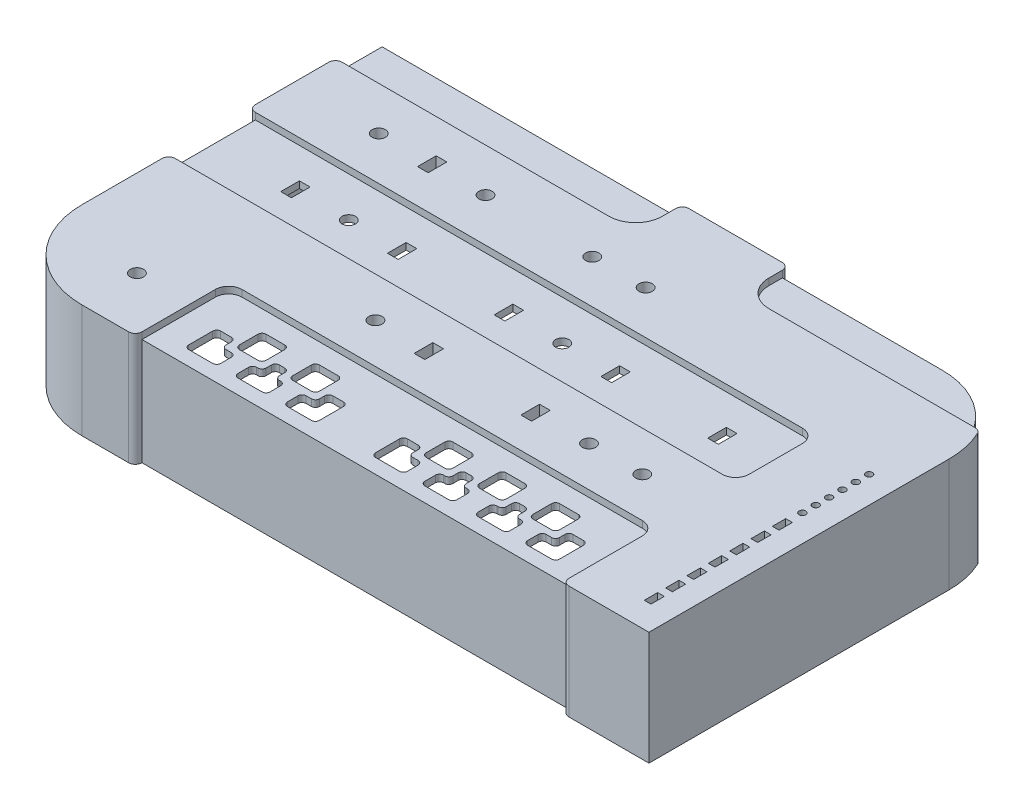
SolidWorks part; units mm, degrees
ref_plane "Front Plane" through (0, 0, 0) normal (0, 0, 1) x (1, 0, 0)
ref_plane "Top Plane" through (0, 0, 0) normal (0, 1, 0) x (1, 0, 0)
ref_plane "Right Plane" through (0, 0, 0) normal (1, 0, 0) x (0, 0, -1)
sketch "Sketch1" plane through (0, 0, 0) normal (0, 1, 0) x (1, 0, 0)
  line L1 (0, 0) -> (240, 0)
  line L2 (0, 0) -> (0, 140)
  line L3 (0, 140) -> (240, 140)
  line L4 (240, 0) -> (240, 140)
  dimension "D1" = 240
  dimension "D2" = 140
extrude "Boss-Extrude1" add sketch "Sketch1" along normal blind 40
fillet "Fillet1" radius 30 2 edges at (240, 20, -140) (0, 20, 0)
sketch "Sketch2" plane through (0, 0, 0) normal (0, -1, 0) x (1, 0, 0)
  line L4 (110, -142.5) -> (110, -125)
  line L5 (110, -125) -> (-2.5, -125)
  line L6 (150, -142.5) -> (150, -125)
  line L7 (150, -125) -> (238.8314, -125)
  line L8 (242.5, -110) -> (242.5, 2.5)
  line L9 (-2.5, -142.5) -> (210, -142.5)
  line L10 (-2.5, -30) -> (-2.5, -142.5)
  line L11 (242.5, 2.5) -> (30, 2.5)
  line L12 (242.5, -110) -> (242.5, 2.5)
  line L13 (110, -142.5) -> (150, -142.5)
  line L14 (-2.5, -30) -> (-2.5, -62.5)
  line L15 (242.5, 2.5) -> (210, 2.5)
  line L16 (-2.5, -92.5) -> (210, -92.5)
  line L17 (210, -92.5) -> (210, -62.5)
  line L18 (210, -62.5) -> (-2.5, -62.5)
  line L19 (50, 2.5) -> (50, -32.5)
  line L20 (50, -32.5) -> (210, -32.5)
  line L21 (210, -32.5) -> (210, 2.5)
  line L22 (210, -140) -> (0, -140) construction
  line L23 (50, 2.5) -> (30, 2.5)
  line L24 (-2.5, -92.5) -> (-2.5, -125)
  arc A4 (210, -142.5) -> (242.5, -110) centre (210, -110) ccw
  arc A5 (30, 2.5) -> (-2.5, -30) centre (30, -30) ccw
  arc A6 (238.8314, -125) -> (242.5, -110) centre (210, -110) ccw
  arc A7 (30, 2.5) -> (-2.5, -30) centre (30, -30) ccw
  point P24 (150, -133.75)
  dimension "D2" = 35
  dimension "D3" = 30
  dimension "D4" = 30
  dimension "D5" = 15
  dimension "D6" = 60
  dimension "D7" = 40
  dimension "D8" = 60
  dimension "D1" = 2.5
extrude "Boss-Extrude2" add sketch "Sketch2" against normal offset from surface (42.5 mm away) 2.5 up to face at (120, 40, -70) offset beyond the face yes
sketch "Sketch3" plane through (0, 0, 0) normal (0, -1, 0) x (1, 0, 0)
  line L38 (2.5, -57.5) -> (5, -57.5)
  line L39 (5, -57.5) -> (5, -97.5)
  line L40 (5, -97.5) -> (2.5, -97.5)
  line L41 (2.5, -97.5) -> (2.5, -120)
  line L42 (2.5, -120) -> (5, -120)
  line L43 (5, -120) -> (5, -135)
  line L44 (5, -135) -> (115, -135)
  line L45 (115, -135) -> (115, -137.5)
  line L46 (115, -137.5) -> (145, -137.5)
  line L47 (145, -137.5) -> (145, -135)
  line L48 (145, -135) -> (210, -135)
  line L49 (232.9129, -120) -> (235.6174, -120)
  line L50 (237.5, -110) -> (237.5, -2.5)
  line L51 (237.5, -2.5) -> (215, -2.5)
  line L52 (215, -2.5) -> (215, -5)
  line L53 (215, -5) -> (45, -5)
  line L54 (45, -5) -> (45, -2.5)
  line L55 (45, -2.5) -> (30, -2.5)
  line L56 (2.5, -30) -> (2.5, -57.5)
  line L57 (2.5, -57.5) -> (5, -57.5)
  line L58 (5, -57.5) -> (5, -97.5)
  line L59 (5, -97.5) -> (2.5, -97.5)
  line L60 (2.5, -97.5) -> (2.5, -120)
  line L61 (2.5, -120) -> (5, -120)
  line L62 (5, -120) -> (5, -135)
  line L63 (5, -135) -> (115, -135)
  line L64 (115, -135) -> (115, -137.5)
  line L65 (115, -137.5) -> (145, -137.5)
  line L66 (145, -137.5) -> (145, -135)
  line L67 (145, -135) -> (210, -135)
  line L68 (232.9129, -120) -> (235.6174, -120)
  line L69 (237.5, -110) -> (237.5, -2.5)
  line L70 (237.5, -2.5) -> (215, -2.5)
  line L71 (215, -2.5) -> (215, -5)
  line L72 (215, -5) -> (45, -5)
  line L73 (45, -5) -> (45, -2.5)
  line L74 (45, -2.5) -> (30, -2.5)
  line L75 (2.5, -30) -> (2.5, -57.5)
  arc A6 (210, -135) -> (232.9129, -120) centre (210, -110) ccw
  arc A7 (235.6174, -120) -> (237.5, -110) centre (210, -110) ccw
  arc A8 (30, -2.5) -> (2.5, -30) centre (30, -30) ccw
  arc A9 (210, -135) -> (232.9129, -120) centre (210, -110) ccw
  arc A10 (235.6174, -120) -> (237.5, -110) centre (210, -110) ccw
  arc A11 (30, -2.5) -> (2.5, -30) centre (30, -30) ccw
  dimension "D1" = 5
extrude "Cut-Extrude1" cut sketch "Sketch3" against normal offset from surface (37.5 mm away) 5 up to face at (122.1113, 42.5, -71.305)
fillet "Fillet2" radius 10 1 edges at (110, 41.25, -125)
fillet "Fillet3" radius 10 1 edges at (150, 41.25, -125)
fillet "Fillet4" radius 5 2 edges at (210, 41.25, -62.5) (210, 41.25, -92.5)
fillet "Fillet5" radius 5 2 edges at (210, 41.25, -32.5) (50, 41.25, -32.5)
fillet "Fillet6" radius 2.5 8 edges at (-2.5, 21.25, -125) (-2.5, 21.25, -92.5) (-2.5, 21.25, -62.5) (50, 21.25, 2.5) (210, 21.25, 2.5) (238.8314, 21.25, -125) (150, 21.25, -142.5) (110, 21.25, -142.5)
sketch "Sketch4" plane through (0, 42.5, 0) normal (0, 1, 0) x (1, 0, 0)
  line L0 (120, 140) -> (120, 0) construction
  line L1 (110, 140) -> (0, 140) construction
  line L2 (50, 0) -> (210, 0) construction
  line L3 (0, 92.5) -> (0, 62.5) construction
  line L4 (50, 0) -> (50, 27.5) construction
  line L5 (48, 112.25) -> (52, 112.25)
  line L6 (48, 112.25) -> (48, 105.25)
  line L7 (48, 105.25) -> (52, 105.25)
  line L8 (52, 112.25) -> (52, 105.25)
  line L9 (28, 81) -> (32, 81)
  line L10 (28, 81) -> (28, 74)
  line L11 (28, 74) -> (32, 74)
  line L12 (32, 81) -> (32, 74)
  line L13 (68, 81) -> (72, 81)
  line L14 (68, 81) -> (68, 74)
  line L15 (68, 74) -> (72, 74)
  line L16 (72, 81) -> (72, 74)
  line L17 (108, 81) -> (112, 81)
  line L18 (108, 81) -> (108, 74)
  line L19 (108, 74) -> (112, 74)
  line L20 (112, 81) -> (112, 74)
  line L21 (148, 81) -> (152, 81)
  line L22 (148, 81) -> (148, 74)
  line L23 (148, 74) -> (152, 74)
  line L24 (152, 81) -> (152, 74)
  line L25 (188, 81) -> (192, 81)
  line L26 (188, 81) -> (188, 74)
  line L27 (188, 74) -> (192, 74)
  line L28 (192, 81) -> (192, 74)
  line L29 (108, 51) -> (112, 51)
  line L30 (108, 51) -> (108, 44)
  line L31 (108, 44) -> (112, 44)
  line L32 (112, 51) -> (112, 44)
  line L33 (148, 51) -> (152, 51)
  line L34 (148, 51) -> (148, 44)
  line L35 (148, 44) -> (152, 44)
  line L36 (152, 51) -> (152, 44)
  line L37 (110, 135) -> (110, 140) construction
  line L38 (110, 140) -> (110, 135) construction
  line L40 (147.5, 142.5) -> (112.5, 142.5) construction
  line L41 (150, 140) -> (150, 135) construction
  line L42 (210, 0) -> (210, 27.5) construction
  line L44 (-2.5, 47.5) -> (242.5, 47.5) construction
  line L45 (-2.5, 60) -> (-2.5, 30) construction
  line L46 (242.5, -2.5) -> (242.5, 110) construction
  line L47 (205, 62.5) -> (0, 62.5) construction
  line L48 (205, 32.5) -> (55, 32.5) construction
  line L49 (0, 77.5) -> (210, 77.5) construction
  line L50 (210, 67.5) -> (210, 87.5) construction
  line L51 (-2.5, 108.75) -> (242.5, 108.75) construction
  line L52 (-2.5, 122.5) -> (-2.5, 95) construction
  circle A0 centre (30, 108.75) radius 2.5
  circle A1 centre (70, 108.75) radius 2.5
  circle A2 centre (110, 108.75) radius 2.5
  circle A3 centre (130, 108.75) radius 2.5
  circle A4 centre (130, 77.5) radius 2.5
  circle A5 centre (190, 47.5) radius 2.5
  circle A6 centre (170, 47.5) radius 2.5
  circle A7 centre (90, 47.5) radius 2.5
  circle A8 centre (30, 18.1) radius 2.5
  circle A9 centre (50, 77.5) radius 2.5
  point P55 (30, 81)
  point P57 (50, 105.25)
  point P58 (150, 74)
  point P59 (70, 81)
  point P60 (150, 51)
  point P61 (110, 81)
  point P62 (110, 51)
  point P63 (110, 74)
  point P64 (190, 74)
  point P71 (70, 74)
  point P74 (110, 137.5)
  point P81 (130, 142.5)
  point P85 (150, 81)
  point P105 (48, 108.75)
  point P107 (28, 77.5)
  point P108 (68, 77.5)
  point P109 (108, 77.5)
  point P110 (148, 77.5)
  point P111 (188, 77.5)
  point P116 (108, 47.5)
  point P117 (148, 47.5)
  dimension "D2" = 5
  dimension "D10" = 20
  dimension "D1" = 120
  dimension "D3" = 4
  dimension "D4" = 7
  dimension "D5" = 20
  dimension "D6" = 20
  dimension "D7" = 20
  dimension "D8" = 20
  dimension "D9" = 18.1
extrude "Cut-Extrude2" cut sketch "Sketch4" against normal through all
sketch "Sketch5" plane through (0, 40, 0) normal (0, 1, 0) x (1, 0, 0)
  line L0 (120, 140) -> (120, 0) construction
  line L1 (110, 140) -> (0, 140) construction
  line L2 (50, 0) -> (210, 0) construction
  line L3 (-2.5, 122.5) -> (-2.5, 95) construction
  line L4 (242.5, -2.5) -> (242.5, 110) construction
  line L5 (85, 32.5) -> (85, 0) construction
  line L6 (70, 25) -> (80, 25)
  line L7 (70, 25) -> (70, 15)
  line L8 (70, 15) -> (80, 15)
  line L9 (80, 25) -> (80, 15)
  line L10 (90, 25) -> (100, 25)
  line L11 (90, 25) -> (90, 15)
  line L12 (90, 15) -> (100, 15)
  line L13 (100, 25) -> (100, 15)
  line L14 (140, 25) -> (150, 25)
  line L15 (140, 25) -> (140, 15)
  line L16 (140, 15) -> (150, 15)
  line L17 (150, 25) -> (150, 15)
  line L18 (160, 25) -> (170, 25)
  line L19 (160, 25) -> (160, 15)
  line L20 (160, 15) -> (170, 15)
  line L21 (170, 25) -> (170, 15)
  line L22 (180, 25) -> (190, 25)
  line L23 (180, 25) -> (180, 15)
  line L24 (180, 15) -> (190, 15)
  line L25 (190, 25) -> (190, 15)
  line L26 (55, 32.5) -> (205, 32.5) construction
  line L27 (205, 32.5) -> (55, 32.5) construction
  line L28 (50, 27.5) -> (50, 0) construction
  line L29 (165, 32.5) -> (165, 0) construction
  point P40 (165, 25)
  dimension "D1" = 10
  dimension "D2" = 10
  dimension "D3" = 35
  dimension "D4" = 5
  dimension "D5" = 7.5
  dimension "D6" = 45
  dimension "D7" = 10
  dimension "D8" = 10
extrude "Cut-Extrude3" cut sketch "Sketch5" against normal through all
sketch "Sketch6" plane through (0, 40, 0) normal (0, 1, 0) x (1, 0, 0)
  line L0 (60.5, 17.5) -> (67.5, 17.5)
  line L1 (67.5, 17.5) -> (67.5, 12.5)
  line L2 (67.5, 12.5) -> (72.5, 12.5)
  line L3 (72.5, 12.5) -> (72.5, 5.5)
  line L4 (72.5, 5.5) -> (60.5, 5.5)
  line L5 (60.5, 5.5) -> (60.5, 17.5)
  line L6 (82.5, 17.5) -> (82.5, 12.5)
  line L7 (82.5, 12.5) -> (79, 12.5)
  line L8 (79, 12.5) -> (79, 5.5)
  line L9 (79, 5.5) -> (91, 5.5)
  line L10 (91, 5.5) -> (91, 12.5)
  line L11 (91, 12.5) -> (87.5, 12.5)
  line L12 (87.5, 12.5) -> (87.5, 17.5)
  line L13 (87.5, 17.5) -> (82.5, 17.5)
  line L14 (97.5, 12.5) -> (102.5, 12.5)
  line L15 (102.5, 12.5) -> (102.5, 17.5)
  line L16 (102.5, 17.5) -> (109.5, 17.5)
  line L17 (109.5, 17.5) -> (109.5, 5.5)
  line L18 (109.5, 5.5) -> (97.5, 5.5)
  line L19 (97.5, 5.5) -> (97.5, 12.5)
  line L20 (137.5, 17.5) -> (137.5, 12.5)
  line L21 (137.5, 12.5) -> (142.5, 12.5)
  line L22 (142.5, 12.5) -> (142.5, 5.5)
  line L23 (142.5, 5.5) -> (130.5, 5.5)
  line L24 (130.5, 5.5) -> (130.5, 17.5)
  line L25 (130.5, 17.5) -> (137.5, 17.5)
  line L26 (152.5, 17.5) -> (152.5, 12.5)
  line L27 (152.5, 12.5) -> (149, 12.5)
  line L28 (149, 12.5) -> (149, 5.5)
  line L29 (149, 5.5) -> (161, 5.5)
  line L30 (161, 5.5) -> (161, 12.5)
  line L31 (161, 12.5) -> (157.5, 12.5)
  line L32 (157.5, 12.5) -> (157.5, 17.5)
  line L33 (157.5, 17.5) -> (152.5, 17.5)
  line L34 (172.5, 17.5) -> (172.5, 12.5)
  line L35 (172.5, 12.5) -> (169, 12.5)
  line L36 (169, 12.5) -> (169, 5.5)
  line L37 (169, 5.5) -> (181, 5.5)
  line L38 (181, 5.5) -> (181, 12.5)
  line L39 (181, 12.5) -> (177.5, 12.5)
  line L40 (177.5, 12.5) -> (177.5, 17.5)
  line L41 (177.5, 17.5) -> (172.5, 17.5)
  line L42 (187.5, 12.5) -> (192.5, 12.5)
  line L43 (192.5, 12.5) -> (192.5, 17.5)
  line L44 (192.5, 17.5) -> (199.5, 17.5)
  line L45 (199.5, 17.5) -> (199.5, 5.5)
  line L46 (199.5, 5.5) -> (187.5, 5.5)
  line L47 (187.5, 5.5) -> (187.5, 12.5)
  line L48 (70, 25) -> (70, 15) construction
  line L49 (70, 15) -> (80, 15) construction
  line L50 (80, 15) -> (80, 25) construction
  line L51 (90, 25) -> (90, 15) construction
  line L52 (100, 15) -> (100, 25) construction
  line L54 (140, 25) -> (140, 15) construction
  line L55 (190, 15) -> (190, 25) construction
  line L56 (150, 15) -> (150, 25) construction
  line L57 (170, 15) -> (170, 25) construction
  point P53 (82.5, 15)
  dimension "D1" = 12
  dimension "D2" = 2.5
  dimension "D3" = 2.5
  dimension "D4" = 12
  dimension "D5" = 2.5
  dimension "D6" = 2.5
  dimension "D7" = 2.5
  dimension "D8" = 2.5
  dimension "D9" = 2.5
  dimension "D10" = 1
  dimension "D11" = 2.5
  dimension "D12" = 2.5
  dimension "D13" = 2.5
  dimension "D14" = 2.5
  dimension "D15" = 2.5
  dimension "D16" = 1
  dimension "D17" = 1
extrude "Cut-Extrude4" cut sketch "Sketch6" against normal through all
fillet "Fillet8" radius 1.5 8 edges at (79, 38.75, -12.5) (82.5, 38.75, -12.5) (82.5, 38.75, -17.5) (102.5, 38.75, -12.5) (102.5, 38.75, -17.5) (90, 38.75, -25) (70, 38.75, -25) (60.5, 38.75, -17.5)
fillet "Fillet9" radius 1.5 9 edges at (109.5, 38.75, -17.5) (100, 38.75, -25) (91, 38.75, -12.5) (87.5, 38.75, -12.5) (87.5, 38.75, -17.5) (80, 38.75, -25) (72.5, 38.75, -12.5) (67.5, 38.75, -12.5) (67.5, 38.75, -17.5)
fillet "Fillet10" radius 1.5 1 edges at (97.5, 38.75, -12.5)
fillet "Fillet11" radius 1.5 13 edges at (192.5, 38.75, -17.5) (192.5, 38.75, -12.5) (187.5, 38.75, -12.5) (169, 38.75, -12.5) (172.5, 38.75, -12.5) (172.5, 38.75, -17.5) (180, 38.75, -25) (160, 38.75, -25) (152.5, 38.75, -17.5) (152.5, 38.75, -12.5) (149, 38.75, -12.5) (140, 38.75, -25) (130.5, 38.75, -17.5)
fillet "Fillet12" radius 1.5 13 edges at (199.5, 38.75, -17.5) (190, 38.75, -25) (181, 38.75, -12.5) (177.5, 38.75, -12.5) (177.5, 38.75, -17.5) (170, 38.75, -25) (161, 38.75, -12.5) (157.5, 38.75, -12.5) (157.5, 38.75, -17.5) (150, 38.75, -25) (142.5, 38.75, -12.5) (137.5, 38.75, -12.5) (137.5, 38.75, -17.5)
fillet "Fillet13" radius 1.5 12 edges at (109.5, 38.75, -5.5) (100, 38.75, -15) (91, 38.75, -5.5) (80, 38.75, -15) (72.5, 38.75, -5.5) (142.5, 38.75, -5.5) (150, 38.75, -15) (161, 38.75, -5.5) (170, 38.75, -15) (181, 38.75, -5.5) (190, 38.75, -15) (199.5, 38.75, -5.5)
fillet "Fillet14" radius 1.5 12 edges at (90, 38.75, -15) (70, 38.75, -15) (60.5, 38.75, -5.5) (79, 38.75, -5.5) (97.5, 38.75, -5.5) (130.5, 38.75, -5.5) (140, 38.75, -15) (149, 38.75, -5.5) (160, 38.75, -15) (169, 38.75, -5.5) (180, 38.75, -15) (187.5, 38.75, -5.5)
sketch "Sketch7" plane through (0, 42.5, 0) normal (0, 1, 0) x (1, 0, 0)
  line L0 (210, 77.5) -> (245.2307, 77.5) construction
  line L1 (231.25, 60) -> (233.75, 60)
  line L2 (231.25, 60) -> (231.25, 55)
  line L3 (231.25, 55) -> (233.75, 55)
  line L4 (233.75, 60) -> (233.75, 55)
  line L5 (231.25, 52) -> (233.75, 52)
  line L6 (231.25, 52) -> (231.25, 47)
  line L7 (231.25, 47) -> (233.75, 47)
  line L8 (233.75, 52) -> (233.75, 47)
  line L9 (231.25, 44) -> (233.75, 44)
  line L10 (231.25, 44) -> (231.25, 39)
  line L11 (231.25, 39) -> (233.75, 39)
  line L12 (233.75, 44) -> (233.75, 39)
  line L13 (231.25, 36) -> (233.75, 36)
  line L14 (231.25, 36) -> (231.25, 31)
  line L15 (231.25, 31) -> (233.75, 31)
  line L16 (233.75, 36) -> (233.75, 31)
  line L17 (231.25, 28) -> (233.75, 28)
  line L18 (231.25, 28) -> (231.25, 23)
  line L19 (231.25, 23) -> (233.75, 23)
  line L20 (233.75, 28) -> (233.75, 23)
  line L21 (231.25, 20) -> (233.75, 20)
  line L22 (231.25, 20) -> (231.25, 15)
  line L23 (231.25, 15) -> (233.75, 15)
  line L24 (233.75, 20) -> (233.75, 15)
  line L25 (231.25, 12) -> (233.75, 12)
  line L26 (231.25, 12) -> (231.25, 7)
  line L27 (231.25, 7) -> (233.75, 7)
  line L28 (233.75, 12) -> (233.75, 7)
  line L29 (210, 87.5) -> (210, 67.5) construction
  line L30 (242.5, -2.5) -> (242.5, 110) construction
  circle A0 centre (232.5, 90) radius 1.25
  circle A1 centre (232.5, 85) radius 1.25
  circle A2 centre (232.5, 80) radius 1.25
  circle A3 centre (232.5, 75) radius 1.25
  circle A4 centre (232.5, 70) radius 1.25
  circle A5 centre (232.5, 65) radius 1.25
  point P42 (232.5, 60)
  point P43 (232.5, 52)
  point P44 (232.5, 55)
  point P45 (232.5, 44)
  point P46 (232.5, 36)
  point P47 (232.5, 28)
  point P48 (232.5, 20)
  point P49 (232.5, 12)
  point P50 (0, 0)
  dimension "D1" = 2.5
  dimension "D2" = 5
  dimension "D3" = 5
  dimension "D4" = 5
  dimension "D5" = 2.5
  dimension "D6" = 5
  dimension "D7" = 5
  dimension "D8" = 3
  dimension "D9" = 3
  dimension "D10" = 3
  dimension "D11" = 3
  dimension "D12" = 3
  dimension "D13" = 3
  dimension "D14" = 10
extrude "Cut-Extrude5" cut sketch "Sketch7" against normal blind 10
